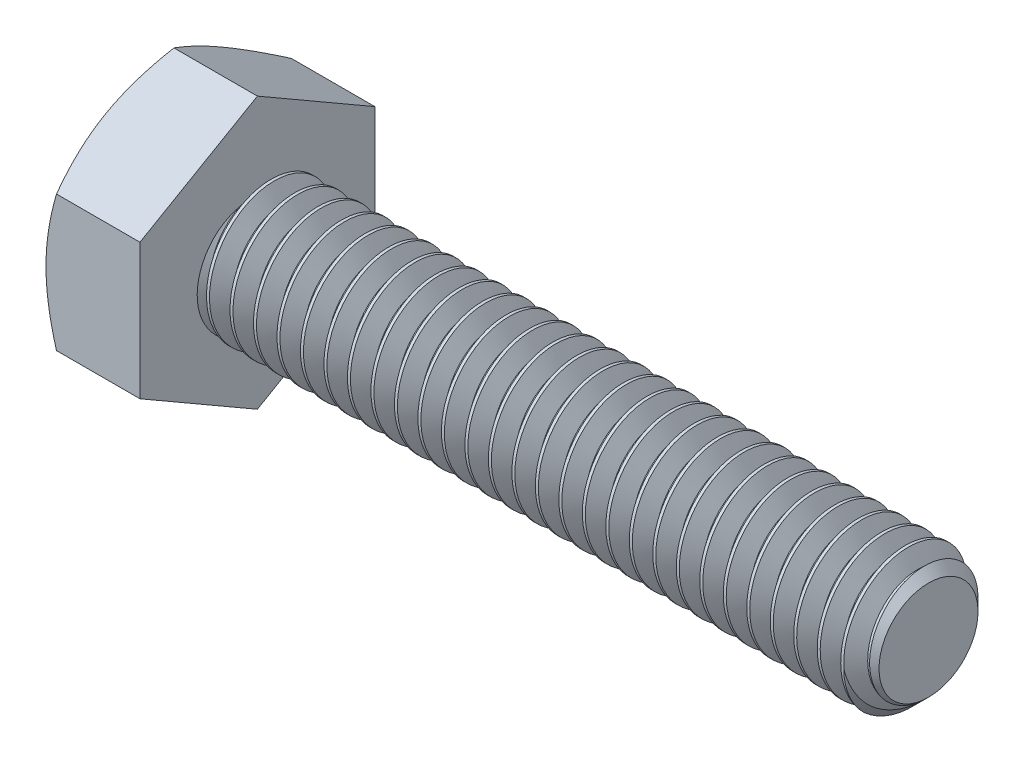
SolidWorks part; units mm, degrees
ref_plane "Front Plane" through (0, 0, 0) normal (0, 0, 1) x (1, 0, 0)
ref_plane "Top Plane" through (0, 0, 0) normal (0, 1, 0) x (1, 0, 0)
ref_plane "Right Plane" through (0, 0, 0) normal (1, 0, 0) x (0, 0, -1)
sketch "Sketch1" plane through (0, 0, 0) normal (0, 0, 1) x (1, 0, 0)
  line L0 (-11.4, 0) -> (11.4, 0) construction
  line L1 (-8.6, 3.5) -> (-8.6, -3.5) construction
  line L2 (-11.4, 3.5) -> (-11.4, -3.5) construction
  line L3 (11.4, 2) -> (11.4, -2) construction
  point P8 (8.95, -2)
  dimension "Thread Dia" = 4
  dimension "Hex" = 7
  dimension "Head Ht" = 2.8
  dimension "Length" = 20
  dimension "D1" = 2.45
ref_plane "Plane2" through (11.4, 0, 0) normal (1, 0, 0) x (0, 0, -1)
sketch "Sketch2" plane through (11.4, 0, 0) normal (1, 0, 0) x (0, 0, -1)
  circle A0 centre (0, 0) radius 2
extrude "Boss-Extrude1" add sketch "Sketch2" against normal up to vertex (20 mm away) up to point (-8.6, -3.5, 0)
sketch "Sketch4" plane through (11.4, 0, 0) normal (1, 0, 0) x (0, 0, -1)
  circle A1 centre (0, 0) radius 2
  circle A2 centre (0, 0) radius 2
  dimension "D1" = 0
curve "Helix/Spiral1" pitch 0.7 height 20.7 turns 29.5714 parameters "Pitch"=0.7
chamfer "Chamfer1" distance 0.525 angle 45 1 edges at (11.4, 0, -2)
sketch "Sketch5" plane through (0, 0, 0) normal (0, 0, 1) x (1, 0, 0)
  line L0 (11.4, 2) -> (11.6625, 1.5453)
  line L1 (11.6625, 1.5453) -> (11.75, 1.5453)
  line L2 (11.75, 1.5453) -> (12.0125, 2)
  line L3 (11.4, 2) -> (12.0125, 2)
  line L4 (11.7062, 1.5453) -> (11.7062, 2) construction
  line L5 (11.5312, 1.7727) -> (11.8812, 1.7727) construction
  line L6 (11.4, -2) -> (11.4, 2) construction
  dimension "D1" = 60
  dimension "D2" = 0.0875
  dimension "D3" = 0.35
sweep "Cut-Sweep1" cut profiles "Sketch5" path "Helix/Spiral1" align with end faces yes
sketch "Sketch3" plane through (-8.6, 0, 0) normal (-1, 0, 0) x (0, 0, 1)
  line L0 (0, 3.5) -> (0, -3.5) construction
  line L1 (-3.5, -2.0207) -> (0, -4.0415)
  line L2 (0, -4.0415) -> (3.5, -2.0207)
  line L3 (3.5, -2.0207) -> (3.5, 2.0207)
  line L4 (3.5, 2.0207) -> (0, 4.0415)
  line L5 (0, 4.0415) -> (-3.5, 2.0207)
  line L6 (-3.5, 2.0207) -> (-3.5, -2.0207)
  circle A0 centre (0, 0) radius 3.5 construction
extrude "Boss-Extrude2" add sketch "Sketch3" along normal up to vertex (2.8 mm away) up to point (-11.4, -3.5, 0)
sketch "Sketch6" plane through (-11.4, 0, 0) normal (-1, 0, 0) x (0, 0, 1)
  circle A0 centre (0, 0) radius 3.5 construction
  circle A1 centre (0, 0) radius 3.5
extrude "Cut-Extrude1" cut sketch "Sketch6" against normal through all draft 60 flip side to cut
sketch "Sketch9" plane through (0, 0, 0) normal (0, 0, 1) x (1, 0, 0)
  line L0 (-8.6, 2) -> (-8.6, 0)
  line L1 (-8.6, 0) -> (-40.6, 0)
  line L2 (-40.6, 0) -> (-42.6, 2)
  line L3 (-42.6, 2) -> (-8.6, 2)
  line L4 (-11.4, 0) -> (11.4, 0) construction
  line L5 (-8.6, 3.5) -> (-8.6, -3.5) construction
  line L6 (11.4, 2) -> (11.4, -2) construction
  dimension "D1" = 45
  dimension "MinThreadLg" = 54
revolve "Revolve1" [suppressed] add sketch "Sketch9" angle 360 about L1
equation "\"D2@Sketch5\" = \"Pitch@Helix/Spiral1\"*.125"
equation "\"D3@Sketch5\" = \"Pitch@Helix/Spiral1\"*.50"
equation "\"D3@Helix/Spiral1\" = \"Length@Sketch1\"+\"Pitch@Helix/Spiral1\""
equation "\"D1@Chamfer1\" = \"Pitch@Helix/Spiral1\"*.750"
equation "\"D1@Sketch1\" = \"Pitch@Helix/Spiral1\"*3.50"
